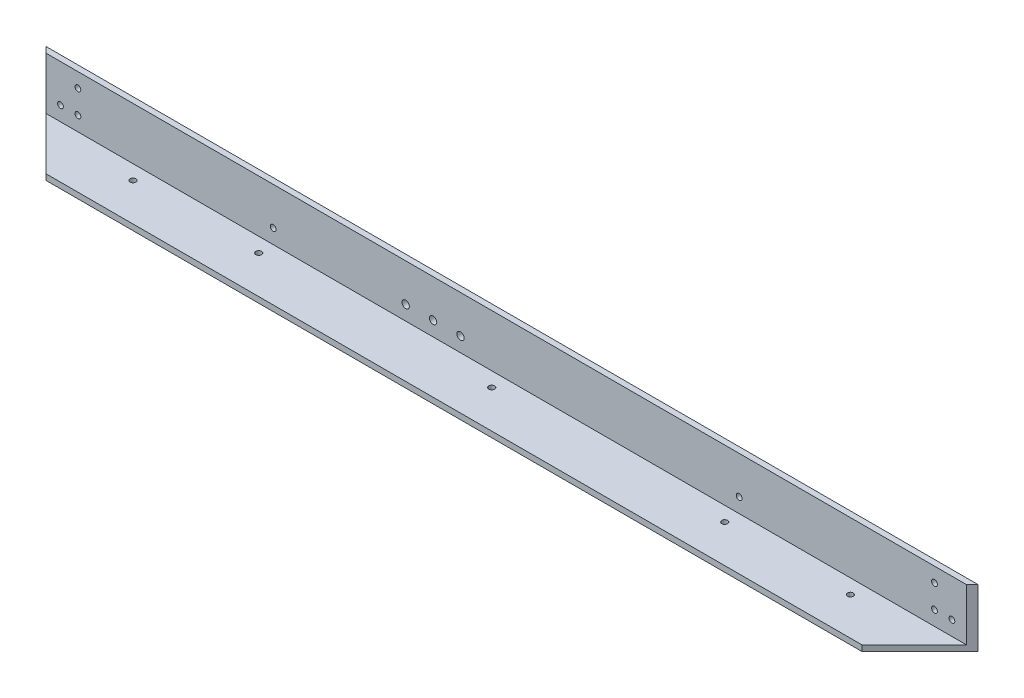
SolidWorks part; units mm, degrees
ref_plane "Front Plane" through (0, 0, 0) normal (0, 0, 1) x (1, 0, 0)
ref_plane "Top Plane" through (0, 0, 0) normal (0, 1, 0) x (1, 0, 0)
ref_plane "Right Plane" through (0, 0, 0) normal (1, 0, 0) x (0, 0, -1)
sketch "Sketch1" plane through (0, 0, 0) normal (1, 0, 0) x (0, 0, -1)
  line L0 (0, 0) -> (-31.75, 0)
  line L1 (-31.75, 0) -> (-31.75, 3.175)
  line L2 (-31.75, 3.175) -> (-3.175, 3.175)
  line L3 (-3.175, 3.175) -> (-3.175, 31.75)
  line L4 (-3.175, 31.75) -> (0, 31.75)
  line L5 (0, 31.75) -> (0, 0)
  dimension "LHeight" = 31.75
  dimension "LWidth" = 31.75
  dimension "LMaterialThickness" = 3.175
  dimension "D1" = 28.575
  dimension "D2" = 28.575
  dimension "D3" = 3.175
extrude "Boss-Extrude1" add sketch "Sketch1" along normal blind 510
chamfer "Chamfer6" distance 31.75 angle 45 1 edges at (510, 1.5875, 31.75)
chamfer "Chamfer7" distance 31.75 angle 45 1 edges at (0, 1.5875, 31.75)
sketch "TopHoles-Sketch3" plane through (0, 3.175, 0) normal (0, 1, 0) x (1, 0, 0)
  line L0 (510, 0) -> (0, 0) construction
  circle A9 centre (451.2625, -11.1125) radius 1.5875
  circle A10 centre (58.7375, -11.1125) radius 1.5875
  circle A13 centre (127.5, -11.1125) radius 1.5875
  circle A14 centre (255, -11.1125) radius 1.5875
  circle A15 centre (382.5, -11.1125) radius 1.5875
  point P8 (0, 0)
  point P9 (0, 0)
  dimension "D5" = 3.175
  dimension "D8" = 127.5
  dimension "D10" = 127.5
  dimension "D11" = 127.5
  dimension "D13" = 68.7625
  dimension "D2" = 11.1125
  dimension "D3" = 58.7375
  dimension "D4" = 58.7375
extrude "TopHoles-Cut-Extrude2" cut sketch "TopHoles-Sketch3" against normal through all
sketch "BackHoles-Sketch4" plane through (0, 0, 3.175) normal (0, 0, 1) x (1, 0, 0)
  line L0 (0, 0) -> (0, 31.75) construction
  line L1 (510, 0) -> (510, 31.75) construction
  line L2 (478.25, 0) -> (31.75, 0) construction
  line L3 (510, 31.75) -> (0, 31.75) construction
  line L7 (510, 0) -> (0, 0) construction
  circle A3 centre (489.3625, 23.8125) radius 1.5875
  circle A4 centre (20.6375, 23.8125) radius 1.5875
  circle A6 centre (11.1125, 11.1125) radius 1.5875
  circle A7 centre (20.6375, 11.1125) radius 1.5875
  circle A8 centre (489.3625, 11.1125) radius 1.5875
  circle A9 centre (498.8875, 11.1125) radius 1.5875
  circle A10 centre (200, 11.1125) radius 2
  circle A11 centre (215, 11.1125) radius 2
  circle A12 centre (230, 11.1125) radius 2
  circle A13 centre (127.5, 11.1125) radius 1.5875
  circle A14 centre (382.5, 11.1125) radius 1.5875
  dimension "D11" = 4
  dimension "D2" = 3.175
  dimension "D7" = 11.1125
  dimension "D6" = 20.6375
  dimension "D5" = 20.6375
  dimension "D8" = 215
  dimension "D9" = 15
  dimension "D10" = 15
  dimension "D12" = 11.1125
  dimension "D13" = 127.5
  dimension "D14" = 127.5
  dimension "D4" = 7.9375
  dimension "D15" = 11.1125
  dimension "D3" = 11.1125
extrude "BackHoles-Cut-Extrude3" cut sketch "BackHoles-Sketch4" against normal through all
equation "\"TopRailWidth\"= 1.25in"
equation "\"TopRailHeight\"= 1.25in"
equation "\"RailThickness\"= .125in'Spec"
equation "\"SideRailHoleY1FromEdge\"= \"HoleOffsetFromEdge\""
equation "\"SideRailHoleX1FromSide\"= \"HoleOffsetFromSide\""
equation "\"VSWidth\"= 1.25in'Spec"
equation "\"HoleOffsetFromEdge\"= \"RailThickness\" * 2.5"
equation "\"HoleOffsetFromSide\"= \"RailThickness\" * 3.5"
equation "\"SideRailHoleX2FromSide\"= \"VSWidth\" - \"HoleOffsetFromEdge\" - \"RailThickness\"'Equals 20.6375"
equation "\"FasteningHoleDiameter\"= .125in"
equation "\"SideRailHoleY2FromSide\"= \"HoleOffsetFromSide\""
equation "\"LWidth@Sketch1\"=\"TopRailWidth\""
equation "\"LHeight@Sketch1\"=\"TopRailHeight\""
equation "\"LMaterialThickness@Sketch1\"=\"RailThickness\""
equation "\"D1@Boss-Extrude1\"= \"FrontBackRailLength\""
equation "\"FrontBackRailLength\"= 510mm"
equation "\"D7@BackHoles-Sketch4\"=\"SideRailHoleY2FromSide\""
equation "\"D1@Chamfer6\"=\"TopRailWidth\""
equation "\"D1@Chamfer7\"=\"TopRailWidth\""
equation "\"D6@BackHoles-Sketch4\"=\"SideRailHoleX2FromSide\""
equation "\"D5@BackHoles-Sketch4\"=\"SideRailHoleX2FromSide\""
equation "\"D8@BackHoles-Sketch4\"=\"FrontBackRailLength\"/2 - 40mm"
equation "\"TopHoleY1FromSide\"= \"HoleOffsetFromSide\""
equation "\"TopCBLength\"= \"TopRailWidth\" * 2'Equals 63.5"
equation "\"FrontOrBackEnclosureOffsets\"= \"FrontBackRailLength\" / 4"
equation "\"D8@TopHoles-Sketch3\"=\"FrontOrBackEnclosureOffsets\""
equation "\"D11@TopHoles-Sketch3\"=\"FrontOrBackEnclosureOffsets\""
equation "\"D10@TopHoles-Sketch3\"=\"FrontOrBackEnclosureOffsets\""
equation "\"D13@BackHoles-Sketch4\"=\"FrontOrBackEnclosureOffsets\""
equation "\"D14@BackHoles-Sketch4\"=\"FrontOrBackEnclosureOffsets\""
equation "\"D2@BackHoles-Sketch4\"=\"FasteningHoleDiameter\""
equation "\"D4@BackHoles-Sketch4\"=\"SideRailHoleY1FromEdge\""
equation "\"D15@BackHoles-Sketch4\"=\"SideRailHoleX1FromSide\""
equation "\"D3@BackHoles-Sketch4\"=\"SideRailHoleX1FromSide\""
equation "\"FrontOrBackCornerEnclosureOffset\"= \"RailThickness\" + \"TopCBLength\" - \"HoleOffsetFromEdge\"'Equals 58.7375"
equation "\"D2@TopHoles-Sketch3\"=\"TopHoleY1FromSide\""
equation "\"D3@TopHoles-Sketch3\"=\"FrontOrBackCornerEnclosureOffset\""
equation "\"D4@TopHoles-Sketch3\"=\"FrontOrBackCornerEnclosureOffset\""
equation "\"D5@TopHoles-Sketch3\"=\"FasteningHoleDiameter\""
